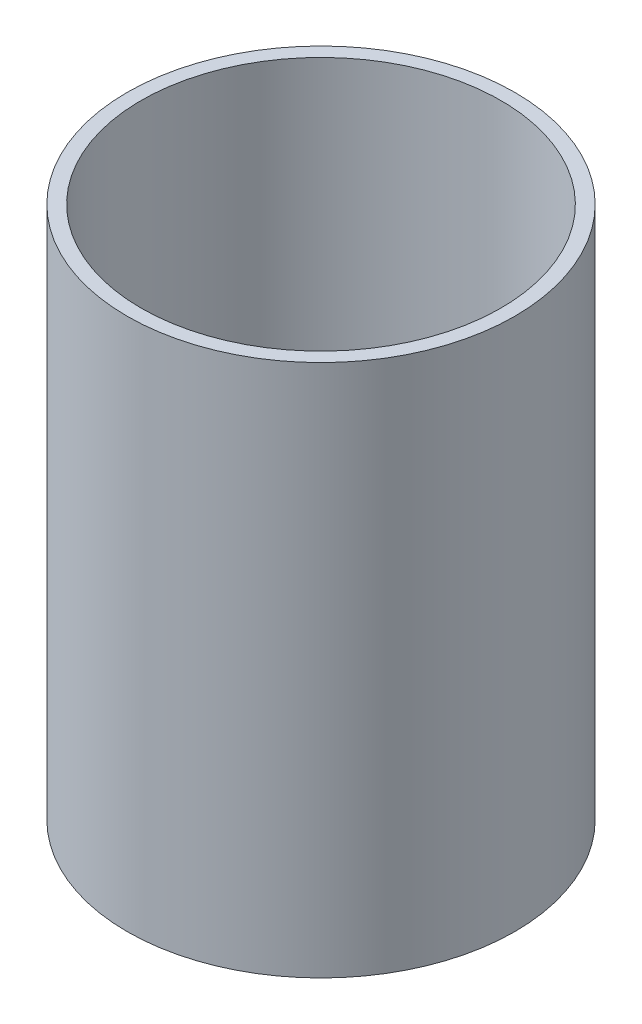
SolidWorks part; units mm, degrees
ref_plane "前基準面" through (0, 0, 0) normal (0, 0, 1) x (1, 0, 0)
ref_plane "上基準面" through (0, 0, 0) normal (0, 1, 0) x (1, 0, 0)
ref_plane "右基準面" through (0, 0, 0) normal (1, 0, 0) x (0, 0, -1)
sketch "草圖6" plane through (0, 0, 0) normal (0, 1, 0) x (1, 0, 0)
  circle A0 centre (0, 0) radius 67.5
  circle A1 centre (0, 0) radius 71.6
  circle A2 centre (0, 0) radius 72.75
  dimension "D1" = 135
  dimension "D2" = 4.1
  dimension "D3" = 145.5
extrude "填料-伸長12" add sketch "草圖6" along normal blind 200 contours A1 A0 | A2 A1 region at (-69.5748, 0, 0) region at (-72.5442, 0, 0)
extrude "填料-伸長13" add sketch "草圖6<12>" along normal blind 2 contours A0 region at (0, 0, 0)
sketch "草圖6<12>" plane through (0, 0, 0) normal (0, 1, 0) x (1, 0, 0) same geometry as "草圖6"
sketch "草圖7" plane through (0, 2, 0) normal (0, 1, 0) x (1, 0, 0)
  line L1 (-34, 34) -> (34, 34)
  line L2 (-34, 34) -> (-34, -34)
  line L3 (-34, -34) -> (34, -34)
  line L4 (34, 34) -> (34, -34)
  line L5 (-34, 34) -> (34, -34) construction
  line L6 (-34, -34) -> (34, 34) construction
  point P0 (0, 0)
  dimension "D1" = 68
sketch "草圖8" plane through (0, 0, 0) normal (0, -1, 0) x (1, 0, 0)
  line L1 (-48.8672, -37.5) -> (26.1328, -37.5)
  line L2 (-48.8672, -37.5) -> (-48.8672, 37.5)
  line L3 (-48.8672, 37.5) -> (26.1328, 37.5)
  line L4 (26.1328, -37.5) -> (26.1328, 37.5)
  line L5 (-48.8672, -37.5) -> (26.1328, 37.5) construction
  line L6 (-48.8672, 37.5) -> (26.1328, -37.5) construction
  point P0 (-11.3672, 0)
  point P5 (0, 0)
  point P6 (-13.2421, 0)
  point P7 (-10.9506, -4.4116)
  point P8 (-8.6591, -2.5368)
  point P9 (-7.6175, 0)
  point P10 (-11.3672, 0)
  dimension "D1" = 75
  dimension "D2" = 75
